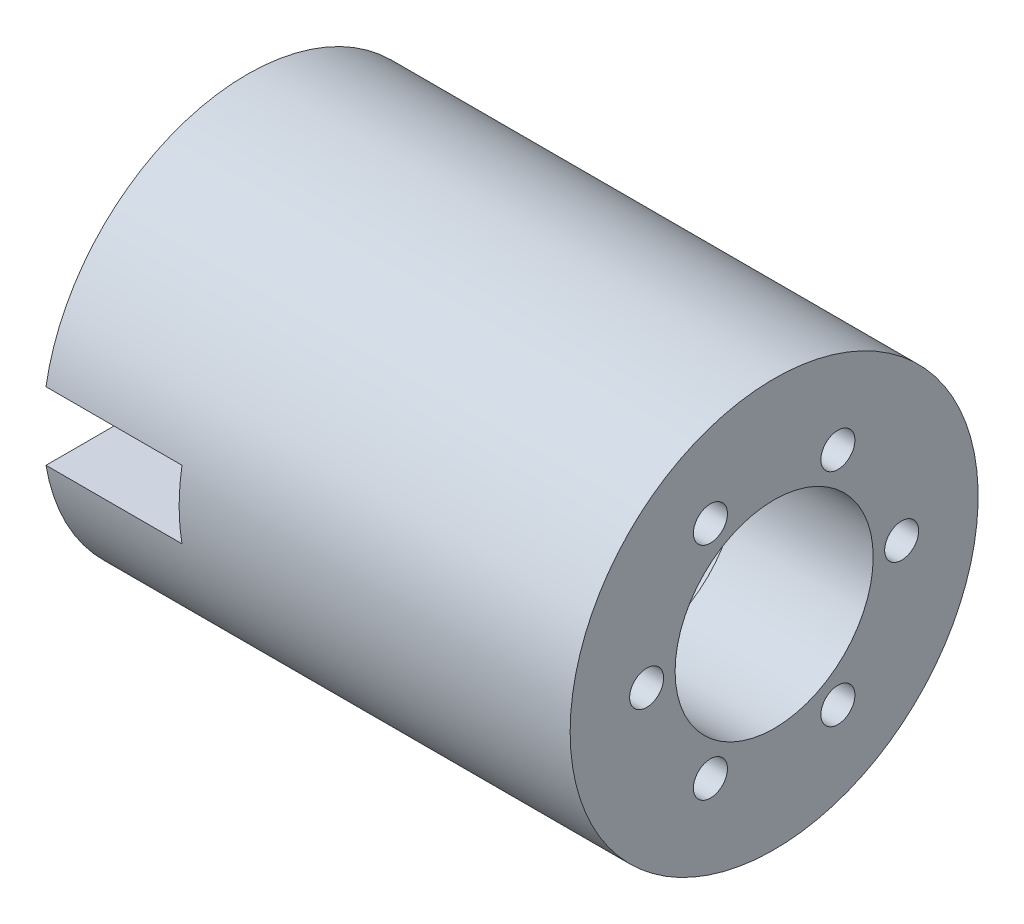
SolidWorks part; units mm, degrees
ref_plane "Front Plane" through (0, 0, 0) normal (0, 0, 1) x (1, 0, 0)
ref_plane "Top Plane" through (0, 0, 0) normal (0, 1, 0) x (1, 0, 0)
ref_plane "Right Plane" through (0, 0, 0) normal (1, 0, 0) x (0, 0, -1)
sketch "Sketch1" plane through (0, 0, 0) normal (0, 0, 1) x (1, 0, 0)
  line L0 (-49.2125, 0) -> (49.2125, 0) construction
  line L1 (0, 0) -> (0, 21.2725) construction
  line L2 (-49.2125, 21.2725) -> (49.2125, 21.2725)
  line L3 (-49.2125, 21.2725) -> (-49.2125, 38.1)
  line L4 (-49.2125, 38.1) -> (42.8625, 38.1)
  line L5 (42.8625, 38.1) -> (42.8625, 76.2)
  line L6 (42.8625, 76.2) -> (49.2125, 76.2)
  line L7 (49.2125, 76.2) -> (49.2125, 21.2725)
  line L8 (42.8625, 38.1) -> (49.2125, 38.1)
  line L9 (23.8125, 21.2725) -> (23.8125, 15.875)
  line L10 (23.8125, 15.875) -> (49.2125, 15.875)
  line L11 (49.2125, 15.875) -> (49.2125, 21.2725)
  point P4 (0, 0)
  point P10 (0, 21.2725)
  dimension "D1" = 6.35
  dimension "D2" = 21.2725
  dimension "D3" = 98.425
  dimension "D4" = 76.2
  dimension "D5" = 38.1
  dimension "D6" = 25.4
  dimension "D7" = 15.875
revolve "Revolve1" add sketch "Sketch1" angle 360 about L0 region at (0, 29.6863, 0) region at (36.5125, 18.5738, 0)
sketch "Sketch2" plane through (49.2125, 0, 0) normal (1, 0, 0) x (0, 0, -1)
  line L0 (-9.316, 41.6349) -> (-4.7427, 53.3559)
  line L1 (31.3989, 28.8853) -> (43.8362, 30.7853)
  line L2 (40.7149, -12.7495) -> (48.5789, -22.5706)
  line L3 (9.316, -41.6349) -> (4.7427, -53.3559)
  line L4 (-31.3989, -28.8853) -> (-43.8362, -30.7853)
  line L5 (-40.7149, 12.7495) -> (-48.5789, 22.5706)
  circle A0 centre (0, 0) radius 80
  circle A1 centre (0, 68) radius 2.5
  circle A2 centre (8.3322, 73.5294) radius 2.5
  circle A3 centre (17.5997, 65.683) radius 2.5
  circle A4 centre (27.0791, 68.8674) radius 2.5
  circle A5 centre (34, 58.8897) radius 2.5
  circle A6 centre (43.9806, 59.5122) radius 2.5
  circle A7 centre (48.0833, 48.0833) radius 2.5
  circle A8 centre (57.8849, 46.1014) radius 2.5
  circle A9 centre (58.8897, 34) radius 2.5
  circle A10 centre (67.8444, 29.5488) radius 2.5
  circle A11 centre (65.683, 17.5997) radius 2.5
  circle A12 centre (73.1805, 10.9825) radius 2.5
  circle A13 centre (68, 0) radius 2.5
  circle A14 centre (73.5294, -8.3322) radius 2.5
  circle A15 centre (65.683, -17.5997) radius 2.5
  circle A16 centre (68.8674, -27.0791) radius 2.5
  circle A17 centre (58.8897, -34) radius 2.5
  circle A18 centre (59.5122, -43.9806) radius 2.5
  circle A19 centre (48.0833, -48.0833) radius 2.5
  circle A20 centre (46.1014, -57.8849) radius 2.5
  circle A21 centre (34, -58.8897) radius 2.5
  circle A22 centre (29.5488, -67.8444) radius 2.5
  circle A23 centre (17.5997, -65.683) radius 2.5
  circle A24 centre (10.9825, -73.1805) radius 2.5
  circle A25 centre (0, -68) radius 2.5
  circle A26 centre (-8.3322, -73.5294) radius 2.5
  circle A27 centre (-17.5997, -65.683) radius 2.5
  circle A28 centre (-27.0791, -68.8674) radius 2.5
  circle A29 centre (-34, -58.8897) radius 2.5
  circle A30 centre (-43.9806, -59.5122) radius 2.5
  circle A31 centre (-48.0833, -48.0833) radius 2.5
  circle A32 centre (-57.8849, -46.1014) radius 2.5
  circle A33 centre (-58.8897, -34) radius 2.5
  circle A34 centre (-67.8444, -29.5488) radius 2.5
  circle A35 centre (-65.683, -17.5997) radius 2.5
  circle A36 centre (-73.1805, -10.9825) radius 2.5
  circle A37 centre (-68, 0) radius 2.5
  circle A38 centre (-73.5294, 8.3322) radius 2.5
  circle A39 centre (-65.683, 17.5997) radius 2.5
  circle A40 centre (-68.8674, 27.0791) radius 2.5
  circle A41 centre (-58.8897, 34) radius 2.5
  circle A42 centre (-59.5122, 43.9806) radius 2.5
  circle A43 centre (-48.0833, 48.0833) radius 2.5
  circle A44 centre (-46.1014, 57.8849) radius 2.5
  circle A45 centre (-34, 58.8897) radius 2.5
  circle A46 centre (-29.5488, 67.8444) radius 2.5
  circle A47 centre (-17.5997, 65.683) radius 2.5
  circle A48 centre (-10.9825, 73.1805) radius 2.5
  circle A49 centre (0, 0) radius 18.5
  circle A50 centre (-11.9063, 20.6222) radius 3.175
  circle A51 centre (11.9063, 20.6222) radius 3.175
  circle A52 centre (23.8125, 0) radius 3.175
  circle A53 centre (11.9063, -20.6222) radius 3.175
  circle A54 centre (-11.9063, -20.6222) radius 3.175
  spline S0 degree 2 poles (5.9532, 60.7088) (27.9941, 58.3228) (43.6425, 42.6185) knots 0 0 0 1 1 1
  spline S1 degree 2 poles (4.0813, 28.8708) (21.9975, 36.8421) (41.5951, 37.5241) knots 0 0 0 1 1 1
  spline S2 degree 1 poles (-10, 38) (-9.316, 41.6349) knots 0 0 1 1
  spline S3 degree 3 poles (-4.7427, 53.3559) (-3.6172, 58.1411) (1.3644, 61.1789) (5.9532, 60.7088) knots 0 0 0 0 1 1 1 1
  spline S4 degree 3 poles (4.0813, 28.8708) (-1.8873, 26.0232) (-10.3042, 30.435) (-10, 38) knots 0 0 0 0 1 1 1 1
  spline S5 degree 2 poles (41.5951, 37.5241) (45.9407, 38.7363) (43.6425, 42.6185) knots 0 0 0 1 1 1
  spline S6 degree 2 poles (53.2944, -17.2603) (56.5169, -20.4176) (58.7299, -16.4862) knots 0 0 0 1 1 1
  spline S7 degree 2 poles (55.552, 25.1988) (64.506, 4.9178) (58.7299, -16.4862) knots 0 0 0 1 1 1
  spline S8 degree 3 poles (43.8362, 30.7853) (48.5431, 32.2031) (53.6647, 29.4078) (55.552, 25.1988) knots 0 0 0 0 1 1 1 1
  spline S9 degree 1 poles (27.909, 27.6603) (31.3989, 28.8853) knots 0 0 1 1
  spline S10 degree 3 poles (27.0435, 10.9008) (21.5931, 14.646) (21.2054, 24.1412) (27.909, 27.6603) knots 0 0 0 0 1 1 1 1
  spline S11 degree 2 poles (27.0435, 10.9008) (42.905, -0.6293) (53.2944, -17.2603) knots 0 0 0 1 1 1
  spline S12 degree 2 poles (11.6993, -54.7845) (10.5763, -59.1539) (15.0875, -59.1047) knots 0 0 0 1 1 1
  spline S13 degree 2 poles (49.5988, -35.51) (36.5119, -53.405) (15.0875, -59.1047) knots 0 0 0 1 1 1
  spline S14 degree 3 poles (48.5789, -22.5706) (52.1602, -25.938) (52.3003, -31.7711) (49.5988, -35.51) knots 0 0 0 0 1 1 1 1
  spline S15 degree 1 poles (37.909, -10.3397) (40.7149, -12.7495) knots 0 0 1 1
  spline S16 degree 3 poles (22.9622, -17.9699) (23.4804, -11.3771) (31.5096, -6.2938) (37.909, -10.3397) knots 0 0 0 0 1 1 1 1
  spline S17 degree 2 poles (22.9622, -17.9699) (20.9075, -37.4715) (11.6993, -54.7845) knots 0 0 0 1 1 1
  spline S18 degree 2 poles (-41.5951, -37.5241) (-45.9407, -38.7363) (-43.6425, -42.6185) knots 0 0 0 1 1 1
  spline S19 degree 2 poles (-5.9532, -60.7088) (-27.9941, -58.3228) (-43.6425, -42.6185) knots 0 0 0 1 1 1
  spline S20 degree 3 poles (4.7427, -53.3559) (3.6172, -58.1411) (-1.3644, -61.1789) (-5.9532, -60.7088) knots 0 0 0 0 1 1 1 1
  spline S21 degree 1 poles (10, -38) (9.316, -41.6349) knots 0 0 1 1
  spline S22 degree 3 poles (-4.0813, -28.8708) (1.8873, -26.0232) (10.3042, -30.435) (10, -38) knots 0 0 0 0 1 1 1 1
  spline S23 degree 2 poles (-4.0813, -28.8708) (-21.9975, -36.8421) (-41.5951, -37.5241) knots 0 0 0 1 1 1
  spline S24 degree 2 poles (-53.2944, 17.2603) (-56.5169, 20.4176) (-58.7299, 16.4862) knots 0 0 0 1 1 1
  spline S25 degree 2 poles (-55.552, -25.1988) (-64.506, -4.9178) (-58.7299, 16.4862) knots 0 0 0 1 1 1
  spline S26 degree 3 poles (-43.8362, -30.7853) (-48.5431, -32.2031) (-53.6647, -29.4078) (-55.552, -25.1988) knots 0 0 0 0 1 1 1 1
  spline S27 degree 1 poles (-27.909, -27.6603) (-31.3989, -28.8853) knots 0 0 1 1
  spline S28 degree 3 poles (-27.0435, -10.9008) (-21.5931, -14.646) (-21.2054, -24.1412) (-27.909, -27.6603) knots 0 0 0 0 1 1 1 1
  spline S29 degree 2 poles (-27.0435, -10.9008) (-42.905, 0.6293) (-53.2944, 17.2603) knots 0 0 0 1 1 1
  spline S30 degree 2 poles (-11.6993, 54.7845) (-10.5763, 59.1539) (-15.0875, 59.1047) knots 0 0 0 1 1 1
  spline S31 degree 2 poles (-49.5988, 35.51) (-36.5119, 53.405) (-15.0875, 59.1047) knots 0 0 0 1 1 1
  spline S32 degree 3 poles (-48.5789, 22.5706) (-52.1602, 25.938) (-52.3003, 31.7711) (-49.5988, 35.51) knots 0 0 0 0 1 1 1 1
  spline S33 degree 1 poles (-37.909, 10.3397) (-40.7149, 12.7495) knots 0 0 1 1
  spline S34 degree 3 poles (-22.9622, 17.9699) (-23.4804, 11.3771) (-31.5096, 6.2938) (-37.909, 10.3397) knots 0 0 0 0 1 1 1 1
  spline S35 degree 2 poles (-22.9622, 17.9699) (-20.9075, 37.4715) (-11.6993, 54.7845) knots 0 0 0 1 1 1
extrude "Cut-Extrude1" cut sketch "Sketch2" against normal blind 25.4 contours A54 | A53 | A52 | A51 | A50 | A54 | A53 | A52 | A49 | A51 | A50 region at (49.2125, 20.6222, 11.9063) region at (49.2125, 20.6222, -11.9063) region at (49.2125, 0, -23.8125) region at (49.2125, -20.6222, -11.9063) region at (49.2125, -20.6222, 11.9063)
pattern_circular "CirPattern1" count 6 over 360 about axis through (-49.2125, 0, 0) along (-1, 0, 0) of "Cut-Extrude1" reverse direction yes
sketch "Sketch3" plane through (0, 0, 0) normal (0, 0, 1) x (1, 0, 0)
  line L0 (0, 0) -> (-49.2125, 0) construction
  line L1 (-49.2125, 38.1) -> (-49.2125, -38.1) construction
  line L2 (-49.2125, -6.35) -> (-49.2125, 6.35)
  line L3 (-49.2125, 6.35) -> (-23.8125, 6.35)
  line L4 (-23.8125, 6.35) -> (-23.8125, -6.35)
  line L5 (-23.8125, -6.35) -> (-49.2125, -6.35)
  point P8 (-49.2125, 0)
  dimension "D1" = 12.7
  dimension "D2" = 25.4
extrude "Cut-Extrude2" cut sketch "Sketch3" along normal through all
